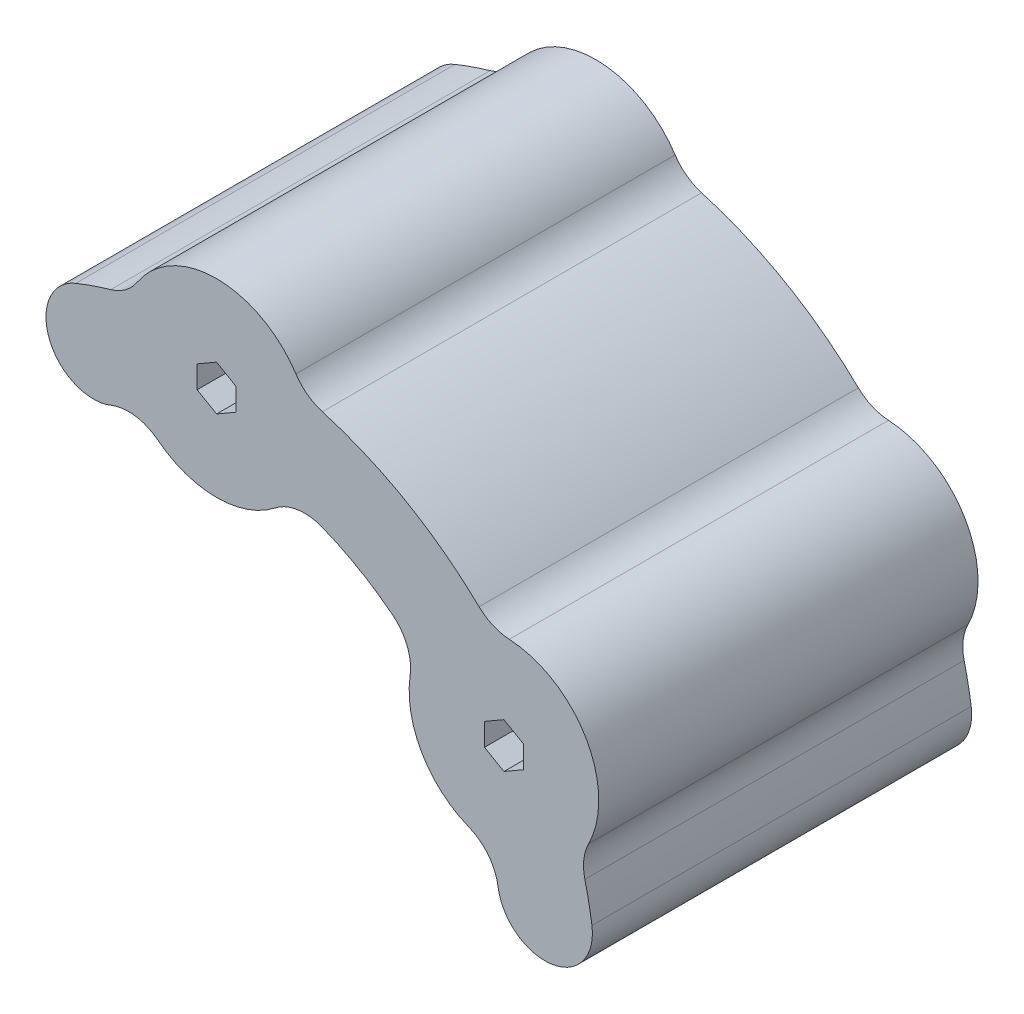
SolidWorks part; units mm, degrees
ref_plane "前视基准面" through (0, 0, 0) normal (0, 0, 1) x (1, 0, 0)
ref_plane "上视基准面" through (0, 0, 0) normal (0, 1, 0) x (1, 0, 0)
ref_plane "右视基准面" through (0, 0, 0) normal (1, 0, 0) x (0, 0, -1)
other "Configuration Table"
sketch "草图1" plane through (0, 0, 0) normal (0, 0, 1) x (1, 0, 0)
  circle A0 centre (0, 0) radius 70 construction
  circle A1 centre (0, 0) radius 60
  circle A2 centre (0, 0) radius 80
  dimension "D1" = 140
  dimension "D2" = 120
  dimension "D3" = 160
extrude "凸台-拉伸1" add sketch "草图1" along normal blind 80
sketch "草图2" plane through (0, 0, 80) normal (0, 0, 1) x (1, 0, 0)
  line L0 (60.6218, 30.2657) -> (64.7218, 32.6329)
  line L1 (4.1, 67.6329) -> (4.1, 72.3671)
  line L2 (4.1, 72.3671) -> (0, 74.7343)
  line L3 (0, 74.7343) -> (-4.1, 72.3671)
  line L4 (-4.1, 72.3671) -> (-4.1, 67.6329)
  line L5 (-4.1, 67.6329) -> (0, 65.2657)
  line L6 (0, 65.2657) -> (4.1, 67.6329)
  line L7 (64.7218, 32.6329) -> (64.7218, 37.3671)
  line L8 (64.7218, 37.3671) -> (60.6218, 39.7343)
  line L9 (60.6218, 39.7343) -> (56.5218, 37.3671)
  line L10 (56.5218, 37.3671) -> (56.5218, 32.6329)
  line L11 (56.5218, 32.6329) -> (60.6218, 30.2657)
  line L12 (56.5218, -37.3671) -> (60.6218, -39.7343)
  line L13 (60.6218, -39.7343) -> (64.7218, -37.3671)
  line L14 (64.7218, -37.3671) -> (64.7218, -32.6329)
  line L15 (64.7218, -32.6329) -> (60.6218, -30.2657)
  line L16 (60.6218, -30.2657) -> (56.5218, -32.6329)
  line L17 (56.5218, -32.6329) -> (56.5218, -37.3671)
  line L18 (-4.1, -67.6329) -> (-4.1, -72.3671)
  line L19 (-4.1, -72.3671) -> (0, -74.7343)
  line L20 (0, -74.7343) -> (4.1, -72.3671)
  line L21 (4.1, -72.3671) -> (4.1, -67.6329)
  line L22 (4.1, -67.6329) -> (0, -65.2657)
  line L23 (0, -65.2657) -> (-4.1, -67.6329)
  line L24 (-60.6218, -30.2657) -> (-64.7218, -32.6329)
  line L25 (-64.7218, -32.6329) -> (-64.7218, -37.3671)
  line L26 (-64.7218, -37.3671) -> (-60.6218, -39.7343)
  line L27 (-60.6218, -39.7343) -> (-56.5218, -37.3671)
  line L28 (-56.5218, -37.3671) -> (-56.5218, -32.6329)
  line L29 (-56.5218, -32.6329) -> (-60.6218, -30.2657)
  line L30 (-56.5218, 37.3671) -> (-60.6218, 39.7343)
  line L31 (-60.6218, 39.7343) -> (-64.7218, 37.3671)
  line L32 (-64.7218, 37.3671) -> (-64.7218, 32.6329)
  line L33 (-64.7218, 32.6329) -> (-60.6218, 30.2657)
  line L34 (-60.6218, 30.2657) -> (-56.5218, 32.6329)
  line L35 (-56.5218, 32.6329) -> (-56.5218, 37.3671)
  circle A0 centre (0, 0) radius 70 construction
  circle A1 centre (0, 70) radius 4.1 construction
  point P12 (-59.2833, 18.543)
  point P13 (0, 0)
  point P43 (0, 0)
  dimension "D1" = 140
  dimension "D2" = 8.2
  dimension "D3" = 6
extrude "切除-拉伸1" cut sketch "草图2" against normal through all
sketch "草图3" plane through (0, 0, 80) normal (0, 0, 1) x (1, 0, 0)
  line L0 (0, 74.7343) -> (64.7218, 37.3671) construction
  line L1 (0, 0) -> (32.3609, 56.0507) construction
  line L2 (0, 0) -> (-40, 69.282)
  line L3 (0, 0) -> (80, 0)
  circle A0 centre (0, 0) radius 80 construction
  arc A1 (-40, 69.282) -> (80, 0) centre (0, 0) ccw
  dimension "D1" = 60
  dimension "D2" = 60
extrude "切除-拉伸2" cut sketch "草图3" against normal through all
sketch "草图4" plane through (0, 0, 80) normal (0, 0, 1) x (1, 0, 0)
  line L0 (0, 0) -> (60.6218, 35) construction
  line L1 (0, 70) -> (0, 0) construction
  circle A0 centre (0, 0) radius 70 construction
  circle A1 centre (0, 70) radius 20
  circle A2 centre (0, 70) radius 7.5
  circle A3 centre (60.6218, 35) radius 7.5
  circle A4 centre (60.6218, 35) radius 20
  dimension "D1" = 140
  dimension "D2" = 40
  dimension "D3" = 15
  dimension "D5" = 15
  dimension "D6" = 40
  dimension "D4" = 60
extrude "凸台-拉伸2" add sketch "草图4" against normal blind 80
fillet "圆角1" radius 10 12 edges at (60, 0, 40) (80, 0, 40) (76.6223, 23.0006, 40) (58.2303, 54.8565, 40) (18.392, 77.8571, 40) (-18.392, 77.8571, 40) (-30, 51.9615, 40) (-15.8919, 57.8571, 40) (15.8919, 57.8571, 40) (42.1598, 42.6913, 40) (58.0517, 15.1658, 40) (-40, 69.282, 40)
